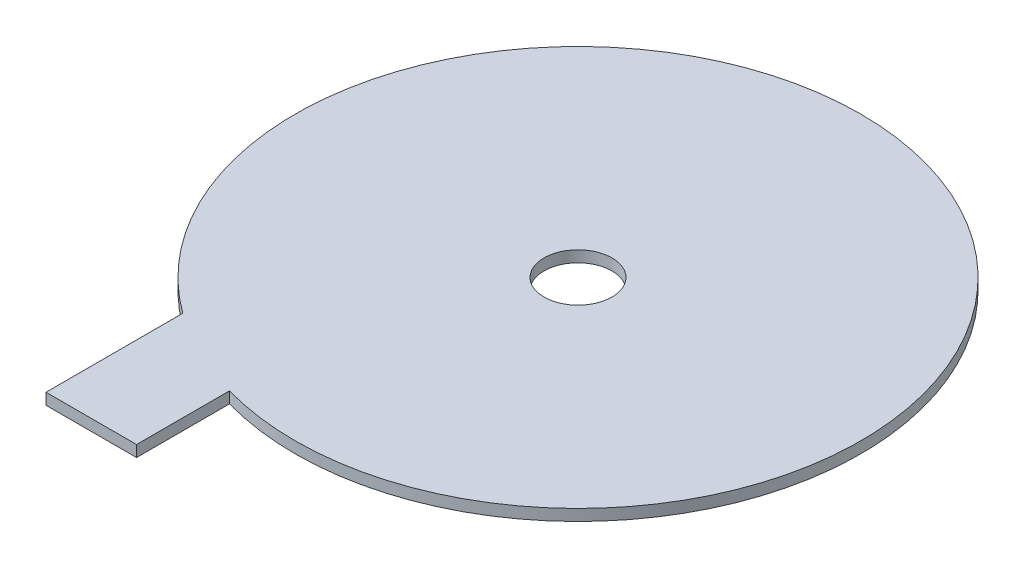
SolidWorks part; units mm, degrees
ref_plane "Front Plane" through (0, 0, 0) normal (0, 0, 1) x (1, 0, 0)
ref_plane "Top Plane" through (0, 0, 0) normal (0, 1, 0) x (1, 0, 0)
ref_plane "Right Plane" through (0, 0, 0) normal (1, 0, 0) x (0, 0, -1)
sketch "Sketch1" plane through (0, 0, 0) normal (0, 1, 0) x (1, 0, 0)
  circle A0 centre (0, 0) radius 50
extrude "Boss-Extrude1" add sketch "Sketch1" along normal blind 2
sketch "Sketch2" plane through (0, 2, 0) normal (0, 1, 0) x (1, 0, 0)
  circle A0 centre (0, 0) radius 6
extrude "Cut-Extrude1" cut sketch "Sketch2" against normal blind 2
sketch "Sketch3" plane through (0, 0, 0) normal (0, -1, 0) x (1, 0, 0)
  line L1 (-29.4445, 0) -> (-13.4445, 0)
  line L2 (-29.4445, 0) -> (-29.4445, 64.5799)
  line L3 (-29.4445, 64.5799) -> (-13.4445, 64.5799)
  line L4 (-13.4445, 0) -> (-13.4445, 64.5799)
  dimension "D1" = 16
  dimension "D2" = 13.4445
  dimension "D3" = 64.5799
extrude "Boss-Extrude2" add sketch "Sketch3" against normal through all
sketch "Sketch4" plane through (0, 2, 0) normal (0, 1, 0) x (1, 0, 0)
  line L4 (-26, -48.23) -> (-26, -61.13)
  line L5 (-20.1, -48.23) -> (-26, -48.23)
  line L6 (-20.1, -61.13) -> (-20.1, -48.23)
  line L7 (-26, -61.13) -> (-20.1, -61.13)
  line L8 (-26, -48.23) -> (-26, -61.13)
  line L9 (-20.1, -48.23) -> (-26, -48.23)
  line L10 (-20.1, -61.13) -> (-20.1, -48.23)
  line L11 (-26, -61.13) -> (-20.1, -61.13)
  dimension "D1" = 0
ref_plane "Plane1" through (20.6197, -108.6, 68.8607) normal (1, 0, 0) x (0, 0, -1)
sketch "Sketch7" plane through (0, 2, 0) normal (0, 1, 0) x (1, 0, 0)
  line L4 (-26, -48.23) -> (-26, -61.13)
  line L5 (-20.1, -48.23) -> (-26, -48.23)
  line L6 (-20.1, -61.13) -> (-20.1, -48.23)
  line L7 (-26, -61.13) -> (-20.1, -61.13)
  line L8 (-26, -48.23) -> (-26, -61.13)
  line L9 (-20.1, -48.23) -> (-26, -48.23)
  line L10 (-20.1, -61.13) -> (-20.1, -48.23)
  line L11 (-26, -61.13) -> (-20.1, -61.13)
  dimension "D1" = 0
